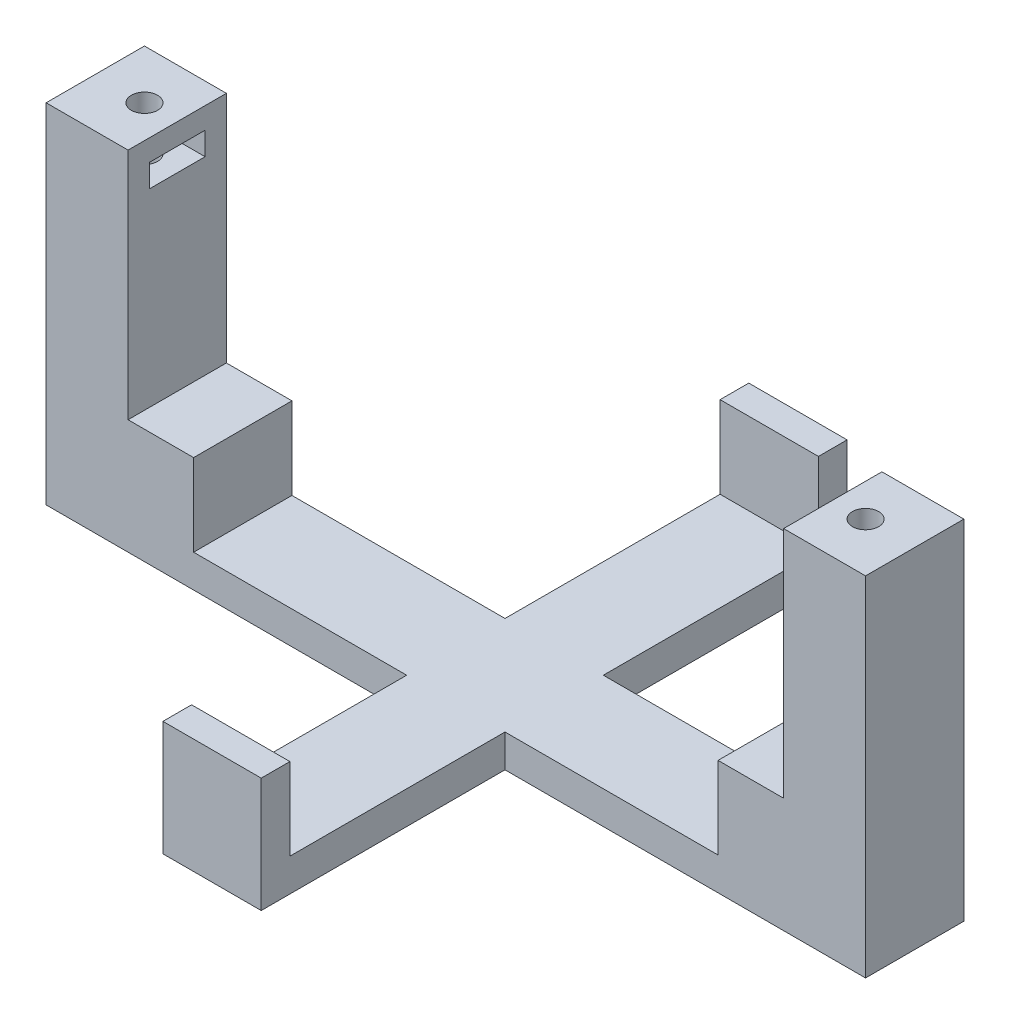
SolidWorks part; units mm, degrees
ref_plane "Front Plane" through (0, 0, 0) normal (0, 0, 1) x (1, 0, 0)
ref_plane "Top Plane" through (0, 0, 0) normal (0, 1, 0) x (1, 0, 0)
ref_plane "Right Plane" through (0, 0, 0) normal (1, 0, 0) x (0, 0, -1)
sketch "Sketch2" plane through (0, 0, 0) normal (0, 1, 0) x (1, 0, 0)
  line L0 (44, 0) -> (-44, 0)
  line L1 (-50, 6) -> (50, 6)
  line L2 (-50, 6) -> (-50, -6)
  line L3 (-50, -6) -> (50, -6)
  line L4 (50, 6) -> (50, -6)
  line L5 (-50, 6) -> (50, -6) construction
  line L6 (-50, -6) -> (50, 6) construction
  line L8 (-6, 35.75) -> (6, 35.75)
  line L9 (-6, 35.75) -> (-6, -35.75)
  line L10 (-6, -35.75) -> (6, -35.75)
  line L11 (6, 35.75) -> (6, -35.75)
  line L12 (-6, 35.75) -> (6, -35.75) construction
  line L13 (-6, -35.75) -> (6, 35.75) construction
  circle A0 centre (-44, 0) radius 1.6
  circle A1 centre (44, 0) radius 1.6
  point P0 (0, 0)
  point P9 (0, 0)
  point P11 (0, 0)
  dimension "D4" = 3.2
  dimension "D5" = 3.2
  dimension "D1" = 100
  dimension "D2" = 12
  dimension "D3" = 88
  dimension "D6" = 12
  dimension "D7" = 71.5
extrude "body" add sketch "Sketch2" along normal blind 4 contours L2 L1 L4 L3 | A0 | A1 | L9 L8 L11 L10
sketch "Sketch4" plane through (0, 4, 0) normal (0, 1, 0) x (1, 0, 0)
  line L0 (-50, -6) -> (-6, -6) construction
  line L1 (-50, 6) -> (-40, 6)
  line L2 (-50, 6) -> (-50, -6)
  line L3 (-50, -6) -> (-40, -6)
  line L4 (-40, 6) -> (-40, -6)
  line L6 (50, 6) -> (40, 6)
  line L7 (50, 6) -> (50, -6)
  line L8 (50, -6) -> (40, -6)
  line L9 (40, 6) -> (40, -6)
  circle A0 centre (-44, 0) radius 1.6
  circle A1 centre (44, 0) radius 1.6
  dimension "D1" = 10
  dimension "D2" = 10
extrude "wings" add sketch "Sketch4" along normal blind 38.5
sketch "Sketch6" plane through (40, 0, 0) normal (-1, 0, 0) x (0, 0, 1)
  line L0 (0, 42.5) -> (0, 38.5)
  line L1 (-6, 42.5) -> (6, 42.5) construction
  line L3 (-3.4, 39.9) -> (3.4, 39.9)
  line L4 (-3.4, 39.9) -> (-3.4, 37.1)
  line L5 (-3.4, 37.1) -> (3.4, 37.1)
  line L6 (3.4, 39.9) -> (3.4, 37.1)
  line L7 (-3.4, 39.9) -> (3.4, 37.1) construction
  line L8 (-3.4, 37.1) -> (3.4, 39.9) construction
  dimension "D1" = 4
  dimension "D2" = 6.8
  dimension "D3" = 2.8
extrude "captive-nut" cut sketch "Sketch6" against normal blind 8.5 contours L6 L3 L4 L5 region at (40, 39.8265, -1.7)
pattern_circular "CirPattern1" count 2 over 360 about axis through (0, 4, 0) along (0, 1, 0) of "captive-nut"
sketch "Sketch8" plane through (0, 4, 0) normal (0, 1, 0) x (1, 0, 0)
  line L0 (6, 35.75) -> (6, 6) construction
  line L1 (-6, 35.75) -> (6, 35.75)
  line L2 (-6, 35.75) -> (-6, 32.25)
  line L3 (-6, 32.25) -> (6, 32.25)
  line L4 (6, 35.75) -> (6, 32.25)
  line L5 (-6, -6) -> (-6, -35.75) construction
  line L6 (6, -35.75) -> (-6, -35.75)
  line L7 (6, -35.75) -> (6, -32.25)
  line L8 (6, -32.25) -> (-6, -32.25)
  line L9 (-6, -35.75) -> (-6, -32.25)
  line L10 (-40, 6) -> (-6, 6) construction
  line L11 (-40, -6) -> (-32, -6)
  line L12 (-40, -6) -> (-40, 6)
  line L13 (-40, 6) -> (-32, 6)
  line L14 (-32, -6) -> (-32, 6)
  line L15 (6, -6) -> (40, -6) construction
  line L16 (40, 6) -> (32, 6)
  line L17 (40, 6) -> (40, -6)
  line L18 (40, -6) -> (32, -6)
  line L19 (32, 6) -> (32, -6)
  dimension "D1" = 3.5
  dimension "D2" = 3.5
  dimension "D3" = 8
  dimension "D4" = 8
extrude "slide-guard" add sketch "Sketch8" along normal blind 10
